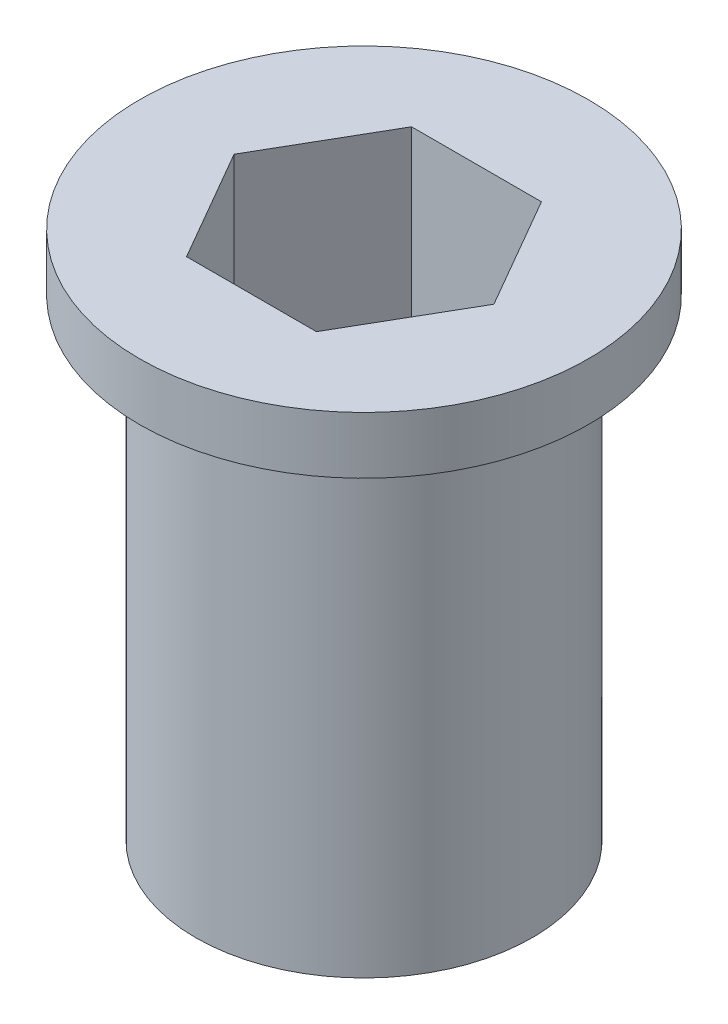
SolidWorks part; units mm, degrees
ref_plane "Front Plane" through (0, 0, 0) normal (0, 0, 1) x (1, 0, 0)
ref_plane "Top Plane" through (0, 0, 0) normal (0, 1, 0) x (1, 0, 0)
ref_plane "Right Plane" through (0, 0, 0) normal (1, 0, 0) x (0, 0, -1)
sketch "Sketch1" plane through (0, 0, 0) normal (0, 1, 0) x (1, 0, 0)
  line L0 (-2.894, -5.0125) -> (2.894, -5.0125)
  line L1 (2.894, -5.0125) -> (5.7879, 0)
  line L2 (5.7879, 0) -> (2.894, 5.0125)
  line L3 (2.894, 5.0125) -> (-2.894, 5.0125)
  line L4 (-2.894, 5.0125) -> (-5.7879, 0)
  line L5 (-5.7879, 0) -> (-2.894, -5.0125)
  circle A0 centre (0, 0) radius 7.5
  circle A1 centre (0, 0) radius 10
  point P7 (0, 0)
  point P9 (0, 5.0125)
  dimension "D3" = 15
  dimension "D4" = 20
  dimension "D1" = 120
  dimension "D2" = 10.025
extrude "Boss-Extrude1" add sketch "Sketch1" against normal blind 21.05 contours A0 L5 L4 L3 L2 L1 L0 region at (-7.2879, 0, 0)
ref_axis "Axis1" through (0, 0, 0) along (0, 1, 0)
extrude "Boss-Extrude2" add sketch "Sketch1<3>" along normal blind 2.54 contours A1 A0 | A0 L5 L4 L3 L2 L1 L0 region at (-7.2879, 0, 0) region at (-9.7172, 0, 0)
sketch "Sketch1<3>" plane through (0, 0, 0) normal (0, 1, 0) x (1, 0, 0) same geometry as "Sketch1"
